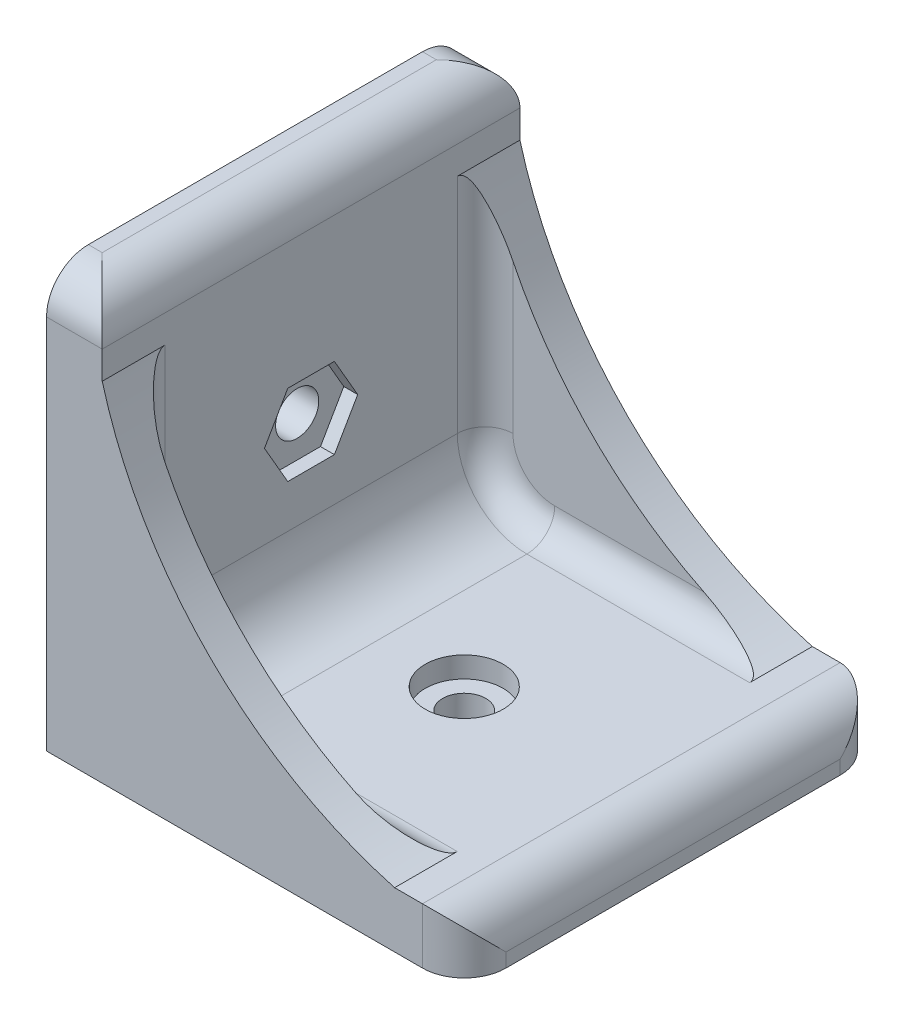
SolidWorks part; units mm, degrees
ref_plane "Alzado" through (0, 0, 0) normal (0, 0, 1) x (1, 0, 0)
ref_plane "Planta" through (0, 0, 0) normal (0, 1, 0) x (1, 0, 0)
ref_plane "Vista lateral" through (0, 0, 0) normal (1, 0, 0) x (0, 0, -1)
sketch "Croquis1" plane through (0, 0, 0) normal (0, 1, 0) x (1, 0, 0)
  line L1 (0, 0) -> (30, 0)
  line L2 (0, 0) -> (0, 30)
  line L3 (0, 30) -> (30, 30)
  line L4 (30, 0) -> (30, 30)
  dimension "D1" = 30
  dimension "D2" = 30
extrude "Saliente-Extruir1" add sketch "Croquis1" along normal blind 30
sketch "Croquis2" plane through (0, 30, 0) normal (0, 1, 0) x (1, 0, 0)
  line L0 (0, 0) -> (30, 0) construction
  line L1 (30, 30) -> (4, 30)
  line L2 (30, 30) -> (30, 0)
  line L3 (30, 0) -> (4, 0)
  line L4 (4, 30) -> (4, 0)
  line L5 (0, 30) -> (0, 0) construction
  dimension "D1" = 4
extrude "Cortar-Extruir1" cut sketch "Croquis2" against normal blind 26
sketch "Croquis3" plane through (4, 0, 0) normal (1, 0, 0) x (0, 0, -1)
  line L0 (15, 30) -> (15, 13.909) construction
  line L1 (30, 30) -> (0, 30) construction
  circle A0 centre (15, 15) radius 1.55
  dimension "D2" = 3.1
  dimension "D1" = 15
extrude "Cortar-Extruir2" cut sketch "Croquis3" against normal up to surface (4 mm away) up to face at (0, 15, -15)
sketch "Croquis4" plane through (0, 4, 0) normal (0, 1, 0) x (1, 0, 0)
  line L0 (30, 15) -> (13.1577, 15) construction
  line L1 (30, 0) -> (30, 30) construction
  circle A0 centre (15, 15) radius 1.55
  dimension "D1" = 3.1
  dimension "D2" = 15
extrude "Cortar-Extruir3" cut sketch "Croquis4" against normal up to surface (4 mm away) up to face at (15, 0, -15)
sketch "Croquis6" plane through (4, 0, 0) normal (1, 0, 0) x (0, 0, -1)
  line L0 (30, 30) -> (0, 30) construction
  line L1 (11.6514, 15) -> (13.3257, 12.1)
  line L2 (13.3257, 12.1) -> (16.6743, 12.1)
  line L3 (16.6743, 12.1) -> (18.3486, 15)
  line L4 (18.3486, 15) -> (16.6743, 17.9)
  line L5 (16.6743, 17.9) -> (13.3257, 17.9)
  line L6 (13.3257, 17.9) -> (11.6514, 15)
  circle A0 centre (15, 15) radius 2.9 construction
  dimension "D1" = 5.8
extrude "Cortar-Extruir5" cut sketch "Croquis6" against normal blind 1
sketch "Croquis7" plane through (0, 0, 0) normal (0, 0, 1) x (1, 0, 0)
  line L0 (4, 4) -> (4, 30) construction
  line L3 (4, 4) -> (30, 4) construction
  line L4 (30, 4) -> (30, 0) construction
  line L5 (25, 4) -> (4, 4)
  line L6 (4, 4) -> (4, 25)
  arc A0 (4, 25) -> (25, 4) centre (32.9323, 32.9323) ccw
  dimension "D2" = 5
  dimension "D3" = 30
  dimension "D1" = 5
extrude "Saliente-Extruir2" add sketch "Croquis7" against normal blind 2.5
sketch "Croquis8" plane through (0, 0, -30) normal (0, 0, -1) x (-1, 0, 0)
  line L0 (-25, 4) -> (-4, 4)
  line L1 (-4, 4) -> (-4, 25)
  arc A0 (-25, 4) -> (-4, 25) centre (-32.9323, 32.9323) ccw construction
  arc A1 (-25, 4) -> (-4, 25) centre (-32.9323, 32.9323) ccw
extrude "Saliente-Extruir3" add sketch "Croquis8" against normal blind 2.5
sketch "Croquis9" plane through (0, 4, 0) normal (0, 1, 0) x (1, 0, 0)
  circle A0 centre (15, 15) radius 2.8
  dimension "D1" = 5.6
extrude "Cortar-Extruir6" cut sketch "Croquis9" against normal blind 1.5
fillet "Redondeo1" radius 5 1 edges at (4, 4, -15)
fillet "Redondeo2" radius 3 6 edges at (30, 4, -15) (4, 30, -15) (2, 30, -30) (2, 30, 0) (30, 2, -30) (30, 2, 0)
fillet "Redondeo3" radius 2 6 edges at (4, 17, -2.5) (5.4645, 5.4645, -2.5) (17, 4, -27.5) (5.4645, 5.4645, -27.5) (17, 4, -2.5) (4, 17, -27.5)
